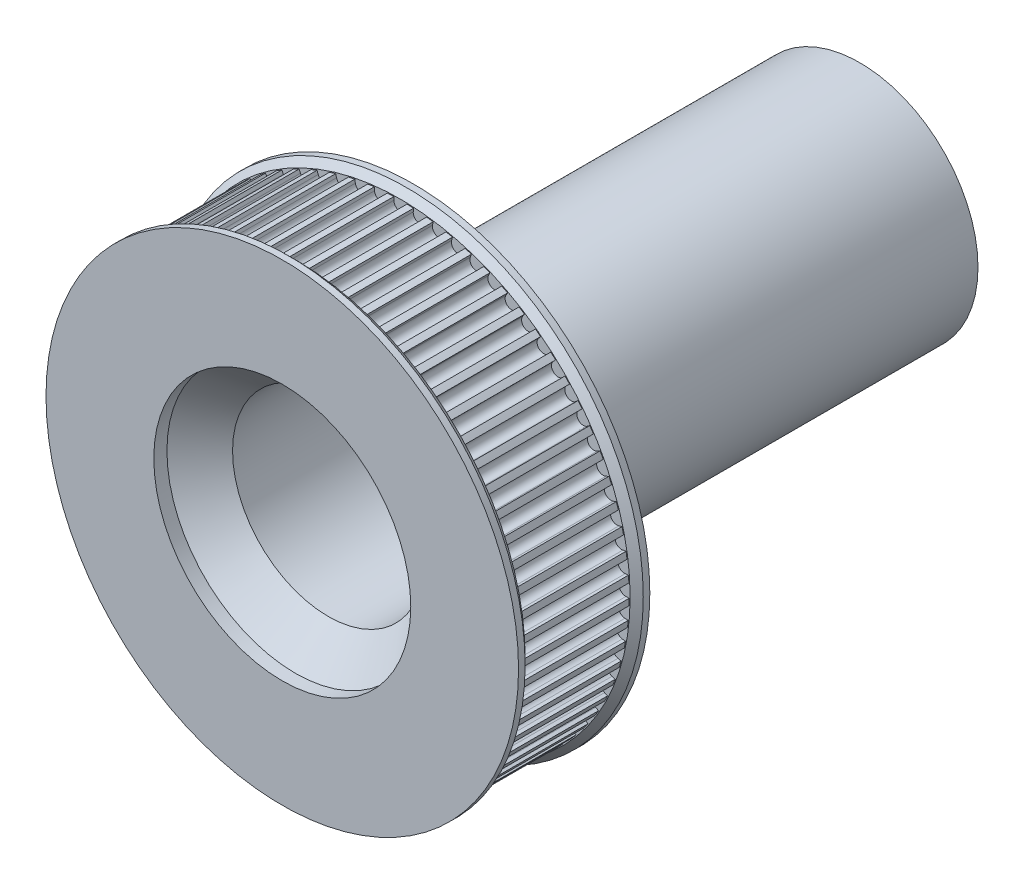
SolidWorks part; units mm, degrees
material "PA Type 6"
ref_plane "Front Plane" through (0, 0, 0) normal (0, 0, 1) x (1, 0, 0)
ref_plane "Top Plane" through (0, 0, 0) normal (0, 1, 0) x (1, 0, 0)
ref_plane "Right Plane" through (0, 0, 0) normal (1, 0, 0) x (0, 0, -1)
sketch "Sketch1" plane through (0, 0, 0) normal (0, 0, 1) x (1, 0, 0)
  circle A0 centre (0, 0) radius 18
extrude "Boss-Extrude1" add sketch "Sketch1" along normal blind 86
sketch "Sketch2" plane through (0, 0, 86) normal (0, 0, 1) x (1, 0, 0)
  circle A0 centre (0, 0) radius 14.576
extrude "Cut-Extrude1" cut sketch "Sketch2" against normal blind 60
sketch "Sketch3" plane through (0, 0, 0) normal (0, 0, -1) x (-1, 0, 0)
  circle A0 centre (0, 0) radius 4.3644
extrude "Cut-Extrude2" cut sketch "Sketch3" against normal blind 60
sketch "Sketch4" plane through (0, 0, 86) normal (0, 0, 1) x (1, 0, 0)
  circle A0 centre (0, 0) radius 14.576
  circle A1 centre (0, 0) radius 34.85
  dimension "D1" = 69.7
extrude "Boss-Extrude2" add sketch "Sketch4" against normal blind 18
sketch "Sketch5" plane through (0, 0, 86) normal (0, 0, 1) x (1, 0, 0)
  circle A0 centre (1.619, -28.1194) radius 3.1814
extrude "Cut-Extrude3" cut sketch "Sketch5" against normal blind 4 from offset 13 offset against normal yes
chamfer "Chamfer2" distance 5 angle 45 1 edges at (14.576, 0, 26)
chamfer "Chamfer3" distance 5 angle 45 1 edges at (14.576, 0, 86)
sketch "Sketch6" plane through (0, 0, 86) normal (0, 0, 1) x (1, 0, 0)
  line L0 (0, 35.6693) -> (0, 34.3375) construction
  line L1 (1, 35.6693) -> (1, 34.3375)
  line L2 (-1, 35.6693) -> (-1, 34.3375)
  arc A0 (1, 35.6693) -> (-1, 35.6693) centre (0, 35.6693) ccw
  arc A1 (-1, 34.3375) -> (1, 34.3375) centre (0, 34.3375) ccw
  point P2 (0, 35.0034)
  point P7 (0, 34.3375)
  dimension "D1" = 1
extrude "Cut-Extrude4" cut sketch "Sketch6" against normal blind 18
pattern_circular "CirPattern1" count 73 over 360 about axis through (0, 0, 86) along (0, 0, 1) of "Cut-Extrude4"
sketch "Sketch7" plane through (0, 0, 86) normal (0, 0, 1) x (1, 0, 0)
  circle A0 centre (0, 0) radius 19.576
  circle A1 centre (0, 0) radius 36
extrude "Boss-Extrude3" add sketch "Sketch7" along normal blind 2
pattern_linear "LPattern1" count 2 spacing 18 along (0, 0, -1) of "Boss-Extrude3"
chamfer "Chamfer4" distance 1 angle 45 2 edges at (36, 0, 86) (36, 0, 70)
